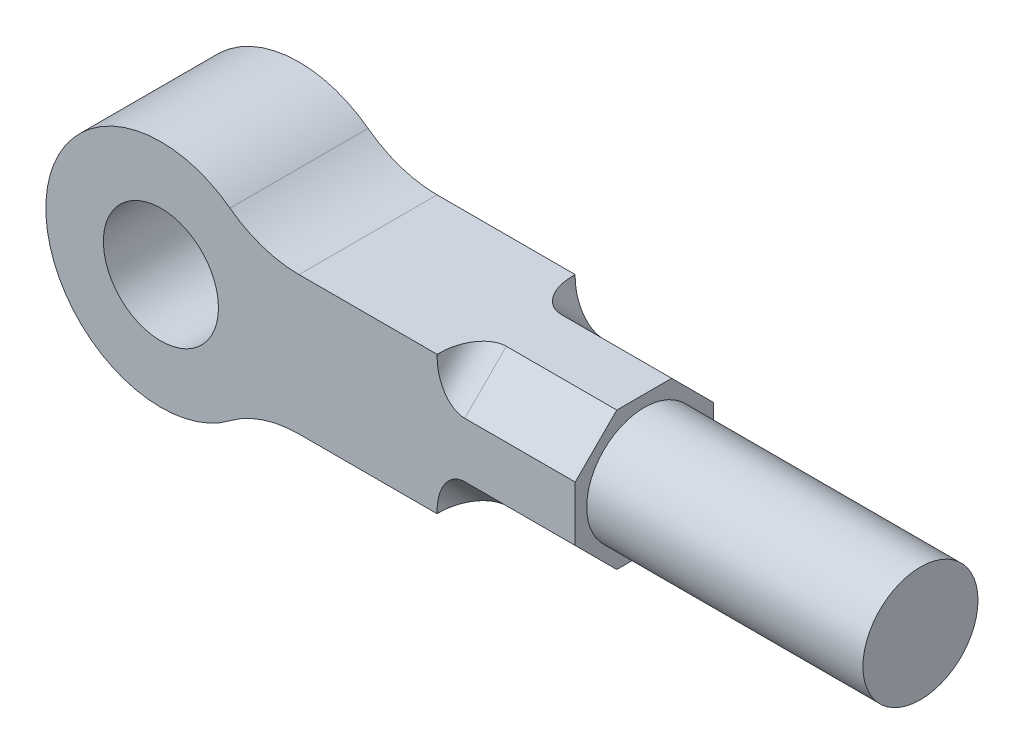
SolidWorks part; units mm, degrees
ref_plane "Front Plane" through (0, 0, 0) normal (0, 0, 1) x (1, 0, 0)
ref_plane "Top Plane" through (0, 0, 0) normal (0, 1, 0) x (1, 0, 0)
ref_plane "Right Plane" through (0, 0, 0) normal (1, 0, 0) x (0, 0, -1)
sketch "Sketch1" plane through (0, 0, 0) normal (0, 0, 1) x (1, 0, 0)
  line L1 (400, 300) -> (1800, 300)
  line L3 (400, -300) -> (1800, -300)
  line L4 (1800, 300) -> (1800, -300)
  arc A0 (400, 300) -> (400, -300) centre (0, 0) ccw
  circle A1 centre (0, 0) radius 250
  dimension "D1" = 500
  dimension "D2" = 1000
  dimension "D3" = 600
  dimension "D4" = 1400
extrude "Boss-Extrude1" add sketch "Sketch1" along normal blind 600
fillet "Fillet1" radius 500 1 edges at (400, 300, 300)
fillet "Fillet2" radius 500 1 edges at (400, -300, 300)
sketch "Sketch2" plane through (1800, 0, 0) normal (1, 0, 0) x (0, 0, -1)
  line L0 (0, -300) -> (0, 300) construction
  line L1 (0, 300) -> (-180.6, 300)
  line L2 (0, 300) -> (-600, 300) construction
  line L3 (-180.6, 300) -> (0, 119.4)
  line L4 (0, 119.4) -> (0, 300)
  line L5 (0, -119.4) -> (-180.6, -300)
  line L6 (0, -300) -> (0, -119.4)
  line L7 (-180.6, -300) -> (0, -300)
  line L8 (-419.4, -300) -> (-600, -119.4)
  line L9 (-600, -300) -> (-419.4, -300)
  line L10 (-600, -119.4) -> (-600, -300)
  line L11 (-600, 119.4) -> (-419.4, 300)
  line L12 (-600, 300) -> (-600, 119.4)
  line L13 (-419.4, 300) -> (-600, 300)
  circle A0 centre (-300, 0) radius 250
  point P22 (-300, 0)
  line M3 (0, -300) -> (0, 300)
  line M4 (0, 300) -> (-600, 300)
  line M5 (-600, 300) -> (-600, -300)
  line M6 (-600, -300) -> (0, -300)
  dimension "D1" = 500
  dimension "D2" = 300
  dimension "D3" = 180.6
  dimension "D4" = 180.6
  dimension "D5" = 4
extrude "Cut-Extrude2" cut sketch "Sketch2" against normal blind 600 contours L11 M5 M4 | L3 M4 M3 | L5 M3 M6 | L8 M6 M5 region at (1800, 239.8, 60.2) region at (1800, 239.8, 539.8) region at (1800, -239.8, 60.2) region at (1800, -239.8, 539.8)
extrude "Boss-Extrude2" add sketch "Sketch2<4>" along normal blind 1200 contours A0 region at (1800, 0, 300)
sketch "Sketch2<4>" plane through (1800, 0, 0) normal (1, 0, 0) x (0, 0, -1) same geometry as "Sketch2"
fillet "Fillet3" radius 120 4 edges at (1200, -209.7, 509.7) (1200, -209.7, 90.3) (1200, 209.7, 90.3) (1200, 209.7, 509.7)
